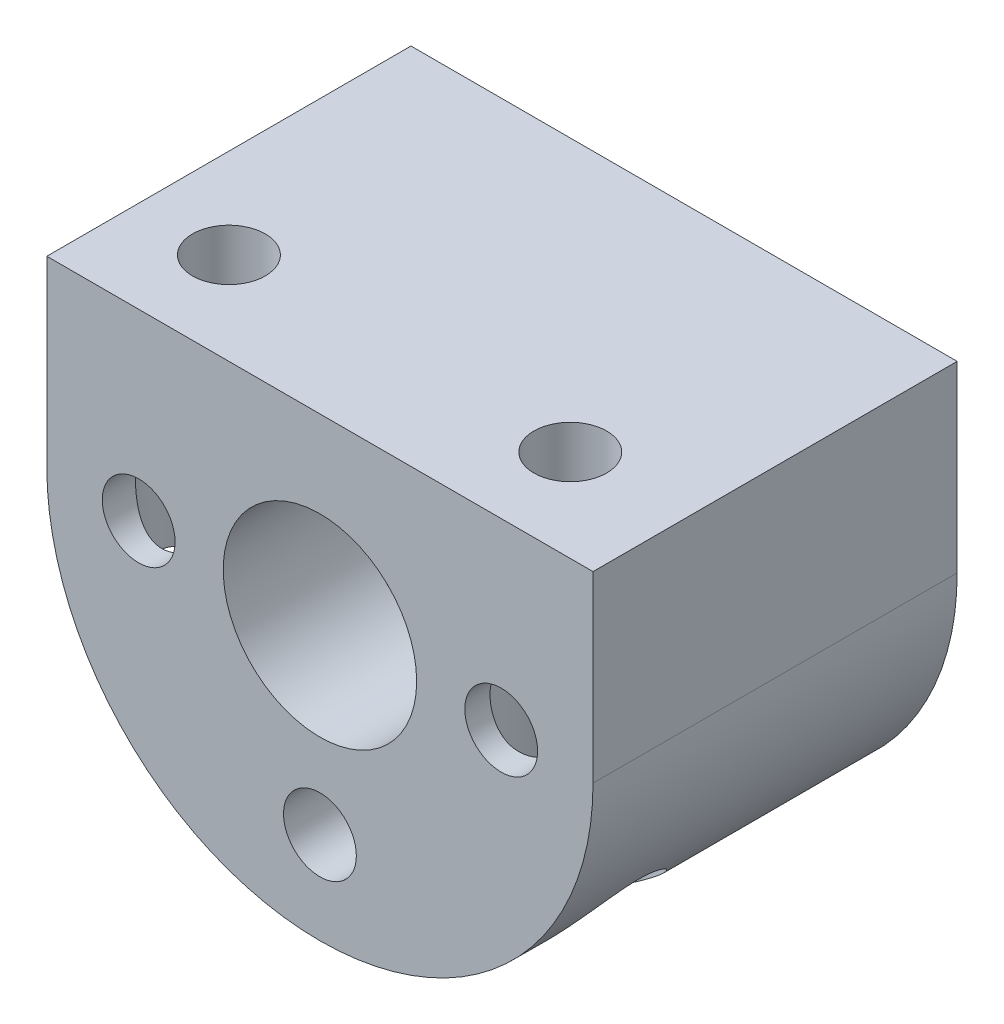
SolidWorks part; units mm, degrees
material "Thornel Mat VMA"
ref_plane "Plano frontal" through (0, 0, 0) normal (0, 0, 1) x (1, 0, 0)
ref_plane "Plano superior" through (0, 0, 0) normal (0, 1, 0) x (1, 0, 0)
ref_plane "Plano direito" through (0, 0, 0) normal (1, 0, 0) x (0, 0, -1)
sketch "Esboço1" plane through (0, 0, 0) normal (0, 0, 1) x (1, 0, 0)
  line L0 (115.6466, -302.7659) -> (115.6466, -295.7159)
  line L1 (92.6466, -295.7159) -> (114.6466, -295.7159) construction
  line L2 (91.6466, -302.7659) -> (91.6466, -295.7159)
  line L3 (92.6466, -302.7659) -> (92.6466, -295.7159) construction
  line L4 (91.6466, -295.7159) -> (115.6466, -295.7159)
  line L5 (114.6466, -302.7659) -> (114.6466, -295.7159) construction
  line L6 (91.6466, -294.7159) -> (115.6466, -294.7159) construction
  line L7 (91.6466, -302.7659) -> (91.6466, -294.7159) construction
  line L8 (115.6466, -302.7659) -> (115.6466, -294.7159) construction
  circle A0 centre (103.6466, -302.7659) radius 7.9647 construction
  arc A1 (92.6466, -302.7659) -> (114.6466, -302.7659) centre (103.6466, -302.7659) ccw construction
  arc A2 (91.6466, -302.7659) -> (115.6466, -302.7659) centre (103.6466, -302.7659) ccw
  dimension "D1" = 11
  dimension "D2" = 1
extrude "Ressalto-extrusão1" add sketch "Esboço1" along normal blind 10 and the other way blind 6
sketch "Sketch4" [suppressed] plane through (0, 0, 9) normal (0, 0, 1) x (1, 0, 0)
  line L1 (92.6466, -295.7159) -> (114.6466, -295.7159)
  line L2 (92.6466, -295.7159) -> (92.6466, -299.8338)
  line L3 (92.6466, -299.8338) -> (114.6466, -299.8338)
  line L4 (114.6466, -295.7159) -> (114.6466, -299.8338)
sketch "Esboço2" plane through (0, 0, 10) normal (0, 0, 1) x (1, 0, 0)
  circle A0 centre (103.6466, -302.7659) radius 5.25
  dimension "10.5" = 10.5
extrude "Corte-extrusão1" cut sketch "Esboço2" against normal blind 31.8 and the other way blind 16
ref_plane "Plane1" through (0, -314.7159, 0) normal (0, 1, 0) x (1, 0, 0)
sketch "Sketch8" plane through (0, 0, 10) normal (0, 0, 1) x (1, 0, 0)
  line L3 (115.6466, -295.7159) -> (91.6466, -295.7159)
  line L4 (115.6466, -295.7159) -> (91.6466, -295.7159)
  line L5 (115.6466, -302.7659) -> (115.6466, -295.7159)
  line L6 (115.6466, -302.7659) -> (115.6466, -295.7159)
  line L7 (91.6466, -295.7159) -> (91.6466, -302.7659)
  line L8 (91.6466, -295.7159) -> (91.6466, -302.7659)
  arc A1 (91.6466, -302.7659) -> (115.6466, -302.7659) centre (103.6466, -302.7659) ccw
  arc A2 (91.6466, -302.7659) -> (115.6466, -302.7659) centre (103.6466, -302.7659) ccw
  dimension "D1" = 0
extrude "Boss-Extrude2" [suppressed] add sketch "Sketch8" along normal blind 5
hole_wizard "M3 Clearance Hole5" positions "Sketch10" profile "Sketch9" hole size "M3" standard "ISO" end condition through all
sketch "Sketch10" plane through (0, 0, 10) normal (0, 0, 1) x (1, 0, 0)
  point P0 (95.6819, -302.7659)
  point P2 (103.6466, -310.7307)
  point P4 (111.6113, -302.7659)
sketch "Sketch9" plane through (95.6819, -302.7659, 10) normal (1, 0, 0) x (0, -1, 0)
  line L0 (0, 0) -> (0, 16)
  line L1 (0, 16) -> (1.6, 16)
  line L2 (1.6, 16) -> (1.6, 0)
  line L5 (1.6, 0) -> (0, 0)
  line L11 (0, -6.35) -> (0, 107.95) construction
  dimension "Thru Hole Dia." = 3.2
  dimension "Thru Hole Depth" = 16
hole_wizard "CBORE for M5 Hex Head Bolt1" positions "Sketch6" profile "Sketch5" counterbore size "M5" standard "DIN" end condition through all
sketch "Sketch6" plane through (0, -314.7159, 0) normal (0, -1, 0) x (-1, 0, 0)
  point P0 (-95.5966, -5.9493)
  point P3 (-110.5966, -5.9493)
sketch "Sketch5" plane through (95.5966, -314.7159, 5.9493) normal (1, 0, 0) x (0, 0, -1)
  line L0 (0, 0) -> (0, 19)
  line L1 (0, 19) -> (1.6, 19)
  line L3 (1.6, 19) -> (1.6, 16.5)
  line L4 (1.6, 16.5) -> (3, 16.5)
  line L5 (3, 16.5) -> (3, 0)
  line L7 (3, 0) -> (0, 0)
  line L11 (0, -6.35) -> (0, 107.95) construction
  dimension "Thru Hole Dia." = 3.2
  dimension "Thru Hole Depth" = 19
  dimension "C'Bore Dia." = 6
  dimension "C'Bore Depth" = 16.5
sketch "Sketch11" plane through (0, -295.7159, 0) normal (0, 1, 0) x (1, 0, 0)
  line L4 (115.6466, 6) -> (91.6466, 6)
  line L5 (91.6466, 6) -> (91.6466, -10)
  line L6 (91.6466, -10) -> (115.6466, -10)
  line L7 (115.6466, -10) -> (115.6466, 6)
  line L8 (115.6466, 6) -> (91.6466, 6)
  line L9 (91.6466, 6) -> (91.6466, -10)
  line L10 (91.6466, -10) -> (115.6466, -10)
  line L11 (115.6466, -10) -> (115.6466, 6)
  circle A0 centre (95.5966, -5.9493) radius 1.6 construction
  circle A1 centre (110.5966, -5.9493) radius 1.6 construction
  circle A2 centre (95.5966, -5.9493) radius 1.6
  circle A3 centre (110.5966, -5.9493) radius 1.6
  dimension "D1" = 0
extrude "Boss-Extrude3" add sketch "Sketch11" along normal blind 1
sketch "Sketch12" plane through (0, 0, 10) normal (0, 0, 1) x (1, 0, 0)
  circle A1 centre (103.6466, -302.7659) radius 5.25
  circle A2 centre (103.6466, -302.7659) radius 4.25
extrude "Boss-Extrude5" add sketch "Sketch12" against normal blind 6
chamfer "Chamfer1" distance 0.3 angle 45 1 edges at (108.8966, -302.7659, -6)
sketch "Sketch13" plane through (0, -298.2159, 0) normal (0, -1, 0) x (1, 0, 0)
  circle A0 centre (95.5966, 5.9493) radius 3 construction
  circle A1 centre (95.5966, 5.9493) radius 3
  circle A2 centre (110.5966, 5.9493) radius 3 construction
  circle A3 centre (110.5966, 5.9493) radius 3
extrude "Cut-Extrude1" cut sketch "Sketch13" along normal blind 43.8
